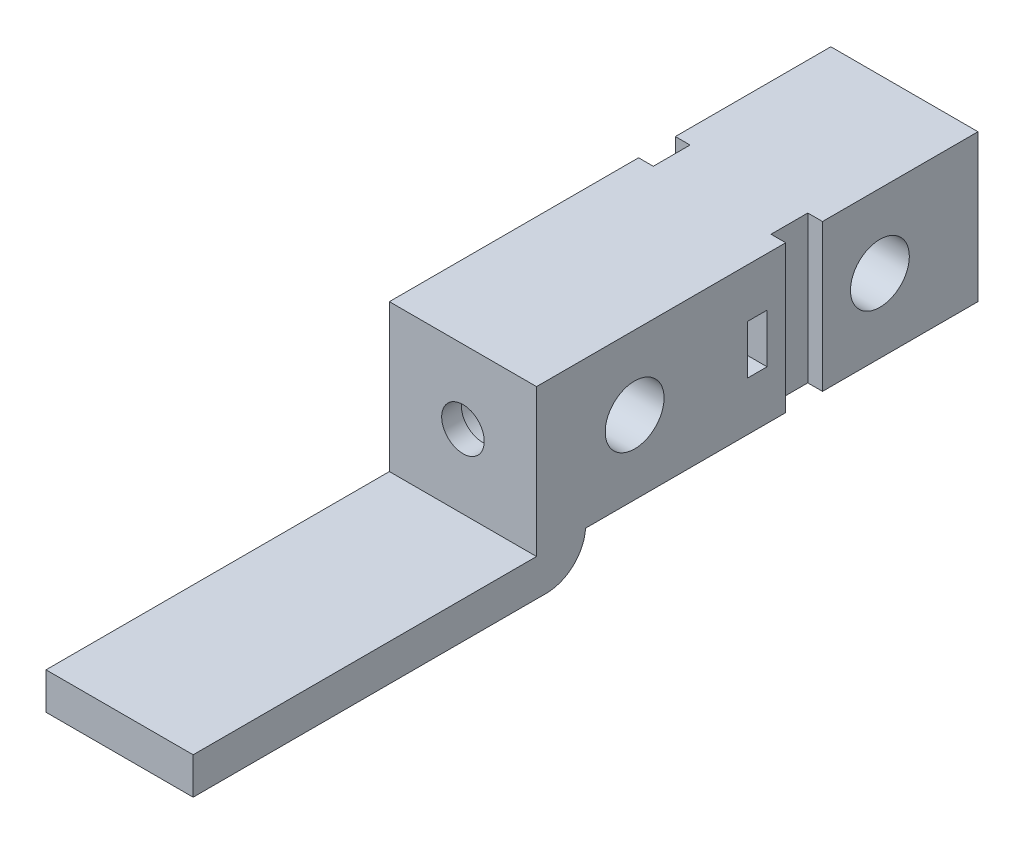
SolidWorks part; units mm, degrees
ref_plane "Front Plane" through (0, 0, 0) normal (0, 0, 1) x (1, 0, 0)
ref_plane "Top Plane" through (0, 0, 0) normal (0, 1, 0) x (1, 0, 0)
ref_plane "Right Plane" through (0, 0, 0) normal (1, 0, 0) x (0, 0, -1)
sketch "Sketch1" plane through (0, 0, 0) normal (0, 0, 1) x (1, 0, 0)
  line L1 (9.525, -9.525) -> (-9.525, -9.525)
  line L2 (9.525, -9.525) -> (9.525, 9.525)
  line L3 (9.525, 9.525) -> (-9.525, 9.525)
  line L4 (-9.525, -9.525) -> (-9.525, 9.525)
  line L5 (9.525, -9.525) -> (-9.525, 9.525) construction
  line L6 (9.525, 9.525) -> (-9.525, -9.525) construction
  point P0 (0, 0)
  dimension "D1" = 19.05
  dimension "D2" = 19.05
extrude "Boss-Extrude1" add sketch "Sketch1" along normal blind 57.15
sketch "Sketch2" plane through (0, 0, 0) normal (0, 0, -1) x (-1, 0, 0)
  circle A0 centre (0, 0) radius 2.7559
  dimension "D1" = 5.5118
extrude "Cut-Extrude1" cut sketch "Sketch2" against normal blind 57.15 contours A0
sketch "Sketch3" plane through (0, 0, 0) normal (0, 0, -1) x (-1, 0, 0)
  circle A0 centre (0, 0) radius 4.445
  dimension "D1" = 8.89
extrude "Cut-Extrude2" cut sketch "Sketch3" against normal blind 54.61
sketch "Sketch4" plane through (9.525, 0, 0) normal (1, 0, 0) x (0, 0, -1)
  line L0 (-44.45, 0) -> (-57.15, 0)
  line L1 (-57.15, -9.525) -> (-57.15, 9.525) construction
  line L2 (-12.7, 0) -> (0, 0)
  line L3 (0, -9.525) -> (0, 9.525) construction
  circle A0 centre (-44.45, 0) radius 3.81
  circle A1 centre (-12.7, 0) radius 3.81
  dimension "D1" = 7.62
  dimension "D3" = 7.62
  dimension "D2" = 12.7
  dimension "D4" = 12.7
extrude "Cut-Extrude3" cut sketch "Sketch4" against normal blind 54.61 contours A1 | A0 region at (9.525, 0, 16.4022)
sketch "Sketch6" plane through (9.525, 0, 0) normal (1, 0, 0) x (0, 0, -1)
  line L0 (0, 0) -> (-57.15, 0) construction
  line L1 (-27.305, -3.175) -> (-29.845, -3.175)
  line L2 (-27.305, -3.175) -> (-27.305, 3.175)
  line L3 (-27.305, 3.175) -> (-29.845, 3.175)
  line L4 (-29.845, -3.175) -> (-29.845, 3.175)
  line L5 (-27.305, -3.175) -> (-29.845, 3.175) construction
  line L6 (-27.305, 3.175) -> (-29.845, -3.175) construction
  line L7 (-57.15, -9.525) -> (-57.15, 9.525) construction
  point P0 (-28.575, 0)
  dimension "D1" = 6.35
  dimension "D2" = 2.54
extrude "Cut-Extrude4" cut sketch "Sketch6" against normal blind 54.61 contours L2 L1 L4 L3
sketch "Sketch7" plane through (0, -9.525, 0) normal (0, -1, 0) x (1, 0, 0)
  line L0 (-9.525, 0) -> (-9.525, 24.892) construction
  line L1 (-9.525, 57.15) -> (-9.525, 0) construction
  line L2 (-9.525, 24.892) -> (9.525, 24.892) construction
  line L3 (9.525, 57.15) -> (9.525, 0) construction
  line L4 (-9.525, 24.892) -> (-7.62, 24.892)
  line L5 (-9.525, 24.892) -> (-9.525, 20.1295)
  line L6 (-9.525, 20.1295) -> (-7.62, 20.1295)
  line L7 (-7.62, 24.892) -> (-7.62, 20.1295)
  line L9 (9.525, 24.892) -> (7.62, 24.892)
  line L10 (9.525, 24.892) -> (9.525, 20.1295)
  line L11 (9.525, 20.1295) -> (7.62, 20.1295)
  line L12 (7.62, 24.892) -> (7.62, 20.1295)
  dimension "D1" = 24.892
  dimension "D2" = 1.905
  dimension "D3" = 4.7625
  dimension "D4" = 1.905
  dimension "D5" = 4.7625
extrude "Cut-Extrude5" cut sketch "Sketch7" against normal blind 54.61
sketch "Sketch8" plane through (0, -9.525, 0) normal (0, -1, 0) x (1, 0, 0)
  line L0 (9.525, 57.15) -> (9.525, 24.892) construction
  line L1 (-9.525, 57.15) -> (9.525, 57.15)
  line L2 (-9.525, 57.15) -> (-9.525, 50.8)
  line L3 (-9.525, 50.8) -> (9.525, 50.8)
  line L4 (9.525, 57.15) -> (9.525, 50.8)
  line L6 (-9.525, 57.15) -> (9.525, 57.15)
  line L7 (-9.525, 57.15) -> (-9.525, 101.6)
  line L8 (-9.525, 101.6) -> (9.525, 101.6)
  line L9 (9.525, 57.15) -> (9.525, 101.6)
  dimension "D1" = 6.35
  dimension "D2" = 44.45
extrude "Boss-Extrude2" add sketch "Sketch8" along normal blind 4.7625 contours L2 L1 L4 L3 | L7 L6 L9 L8
fillet "Fillet1" radius 5.08 1 edges at (0, -14.2875, 50.8)
